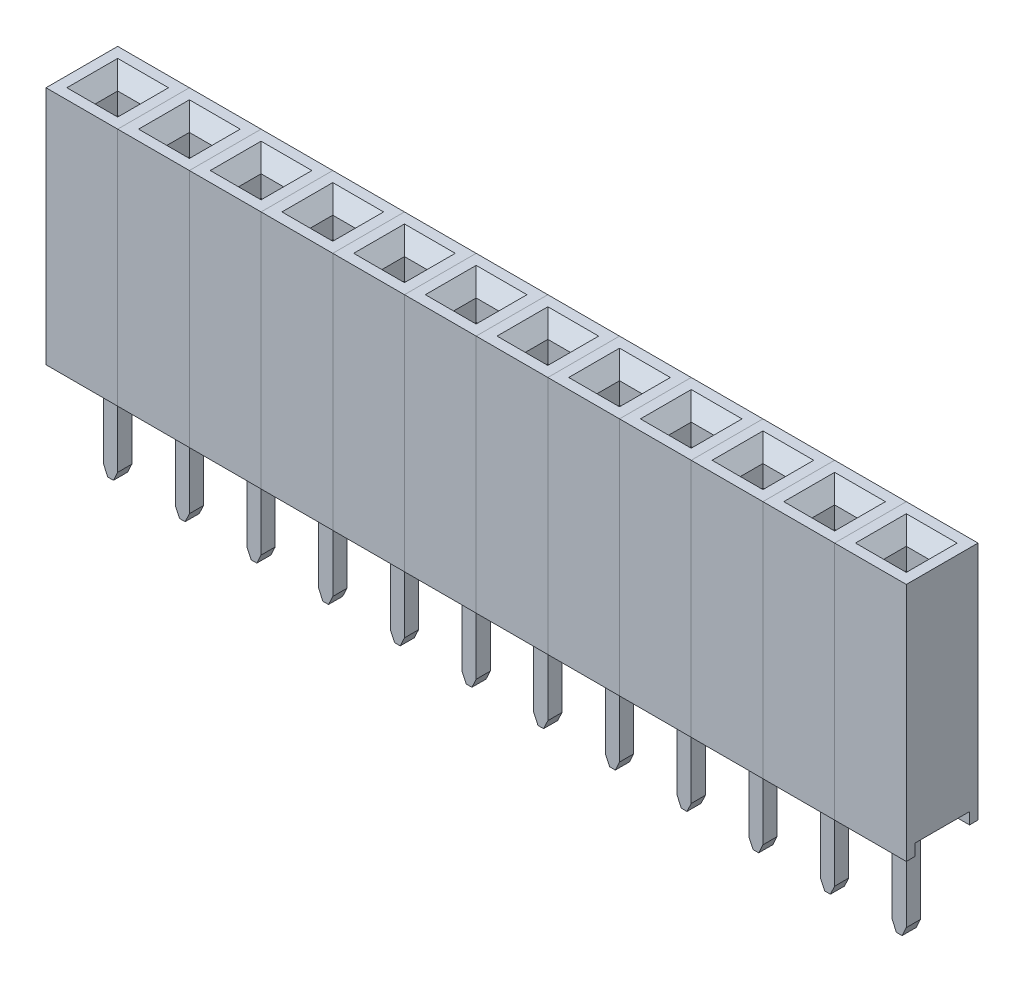
SolidWorks part; units mm, degrees
ref_plane "Front" through (0, 0, 0) normal (0, 0, 1) x (1, 0, 0)
ref_plane "Top" through (0, 0, 0) normal (0, 1, 0) x (1, 0, 0)
ref_plane "Right" through (0, 0, 0) normal (1, 0, 0) x (0, 0, -1)
sketch "Sketch1" plane through (0, 0, 0) normal (0, 0, 1) x (1, 0, 0)
  line L1 (1.27, -4.25) -> (-1.27, -4.25)
  line L2 (1.27, -4.25) -> (1.27, 4.25)
  line L3 (1.27, 4.25) -> (-1.27, 4.25)
  line L4 (-1.27, -4.25) -> (-1.27, 4.25)
  line L5 (1.27, -4.25) -> (-1.27, 4.25) construction
  line L6 (1.27, 4.25) -> (-1.27, -4.25) construction
  point P0 (0, 0)
  dimension "D1" = 2.54
  dimension "D2" = 8.5
extrude "Boss-Extrude1" add sketch "Sketch1" along normal mid plane 2.54
sketch "Sketch2" plane through (0, 0, 0) normal (1, 0, 0) x (0, 0, -1)
  line L0 (-0.97, -4.25) -> (0.97, -4.25)
  line L1 (-1.27, -4.25) -> (1.27, -4.25) construction
  line L2 (0.97, -4.25) -> (0.97, -3.8396)
  line L3 (0.97, -3.8396) -> (-0.97, -3.8396)
  line L4 (-0.97, -3.8396) -> (-0.97, -4.25)
  line L5 (1.27, -4.25) -> (1.27, 4.25) construction
  line L6 (-1.27, -4.25) -> (-1.27, 4.25) construction
  dimension "D1" = 0.3
  dimension "D2" = 0.3
extrude "Cut-Extrude1" cut sketch "Sketch2" against normal mid plane 100
sketch "Sketch4" plane through (0, 4.25, 0) normal (0, 1, 0) x (1, 0, 0)
  line L0 (-1.27, 0) -> (1.27, 0) construction
  line L1 (-1.27, -1.27) -> (-1.27, 1.27) construction
  line L2 (1.27, -1.27) -> (1.27, 1.27) construction
  line L4 (-0.875, 0.875) -> (0.875, 0.875)
  line L5 (-0.875, 0.875) -> (-0.875, -0.875)
  line L6 (-0.875, -0.875) -> (0.875, -0.875)
  line L7 (0.875, 0.875) -> (0.875, -0.875)
  line L8 (-0.875, 0.875) -> (0.875, -0.875) construction
  line L9 (-0.875, -0.875) -> (0.875, 0.875) construction
  line L10 (-0.4, 0.4) -> (0.4, 0.4)
  line L11 (-0.4, 0.4) -> (-0.4, -0.4)
  line L12 (-0.4, -0.4) -> (0.4, -0.4)
  line L13 (0.4, 0.4) -> (0.4, -0.4)
  line L14 (-0.4, 0.4) -> (0.4, -0.4) construction
  line L15 (-0.4, -0.4) -> (0.4, 0.4) construction
  point P6 (0, 0)
  point P11 (0, 0)
  point P16 (0, 0)
  dimension "D1" = 1.75
  dimension "D2" = 0.8
extrude "Cut-Extrude2" cut sketch "Sketch4" against normal blind 1.5 contours L13 L10 L11 L12 region at (0, 4.25, 0)
chamfer "Chamfer1" distance 0.5 angle 45 4 edges at (0, 4.25, -0.4) (-0.4, 4.25, 0) (0, 4.25, 0.4) (0.4, 4.25, 0)
sketch "Sketch5" plane through (0, 0, 0) normal (0, 1, 0) x (1, 0, 0)
  line L1 (-0.9, 0.9) -> (0.9, 0.9)
  line L2 (-0.9, 0.9) -> (-0.9, -0.9)
  line L3 (-0.9, -0.9) -> (0.9, -0.9)
  line L4 (0.9, 0.9) -> (0.9, -0.9)
extrude "Cut-Extrude3" cut sketch "Sketch5" against normal blind 3 and the other way blind 3
sketch "Sketch9" plane through (0, 0, 0) normal (0, 0, 1) x (1, 0, 0)
  line L0 (0, 1.6008) -> (0, -6.2684) construction
  line L1 (0.8528, -1.3416) -> (0.6022, -1.2609)
  line L2 (0.6022, -1.2609) -> (0.4133, 1.4919)
  line L3 (0.2803, 1.3393) -> (0.5075, -1.9717)
  line L4 (0.8528, -1.3416) -> (0.8528, -2.6933)
  line L5 (0.8528, -2.6933) -> (0.2807, -3.0533)
  line L6 (0.2807, -3.0533) -> (-0.2807, -3.0533)
  line L7 (-0.8528, -2.6933) -> (-0.2807, -3.0533)
  line L8 (-0.8528, -1.3416) -> (-0.8528, -2.6933)
  line L9 (-0.8528, -1.3416) -> (-0.6022, -1.2609)
  line L10 (-0.6022, -1.2609) -> (-0.4133, 1.4919)
  line L11 (-0.2803, 1.3393) -> (-0.5075, -1.9717)
  line L12 (-0.1, -7.6212) -> (0.1, -7.6212)
  line L13 (0.1, -7.6212) -> (0.25, -7.2995)
  line L14 (0.25, -7.2995) -> (0.25, -3.0533)
  line L15 (-0.1, -7.6212) -> (-0.25, -7.2995)
  line L16 (-0.25, -7.2995) -> (-0.25, -3.0533)
  line L19 (0, 0) -> (0, -10.2857) construction
  arc A0 (0.4133, 1.4919) -> (0.2803, 1.3393) centre (0.2705, 1.4821) ccw
  arc A1 (0.5075, -1.9717) -> (0, -2.3943) centre (0.101, -1.9996) cw
  arc A2 (-0.5075, -1.9717) -> (0, -2.3943) centre (-0.101, -1.9996) ccw
  arc A3 (-0.4133, 1.4919) -> (-0.2803, 1.3393) centre (-0.2705, 1.4821) cw
  point P16 (0, -3.0533)
  point P24 (-0.25, -4.3212)
  dimension "D1" = 115
  dimension "D2" = 115
  dimension "D3" = 0.25
  dimension "D4" = 0.2
  dimension "D5" = 0.25
  dimension "D6" = 3.3
extrude "Boss-Extrude4" add sketch "Sketch9" along normal mid plane 1.7 contours A1 L0 L6 L5 L4 L1 L2 A0 L3 | L0 A2 L11 A3 L10 L9 L8 L7 L6 region at (0.803, -2.0175, 0)
extrude "Boss-Extrude5" add sketch "Sketch9<3>" along normal mid plane 0.5 contours L16 L15 L12 L13 L14 L6 region at (0, -5.2903, 0)
sketch "Sketch9<3>" plane through (0, 0, 0) normal (0, 0, 1) x (1, 0, 0) same geometry as "Sketch9"
pattern_linear "LPattern1" count 12 spacing 2.54 along (1, 0, 0) of bodies 108
